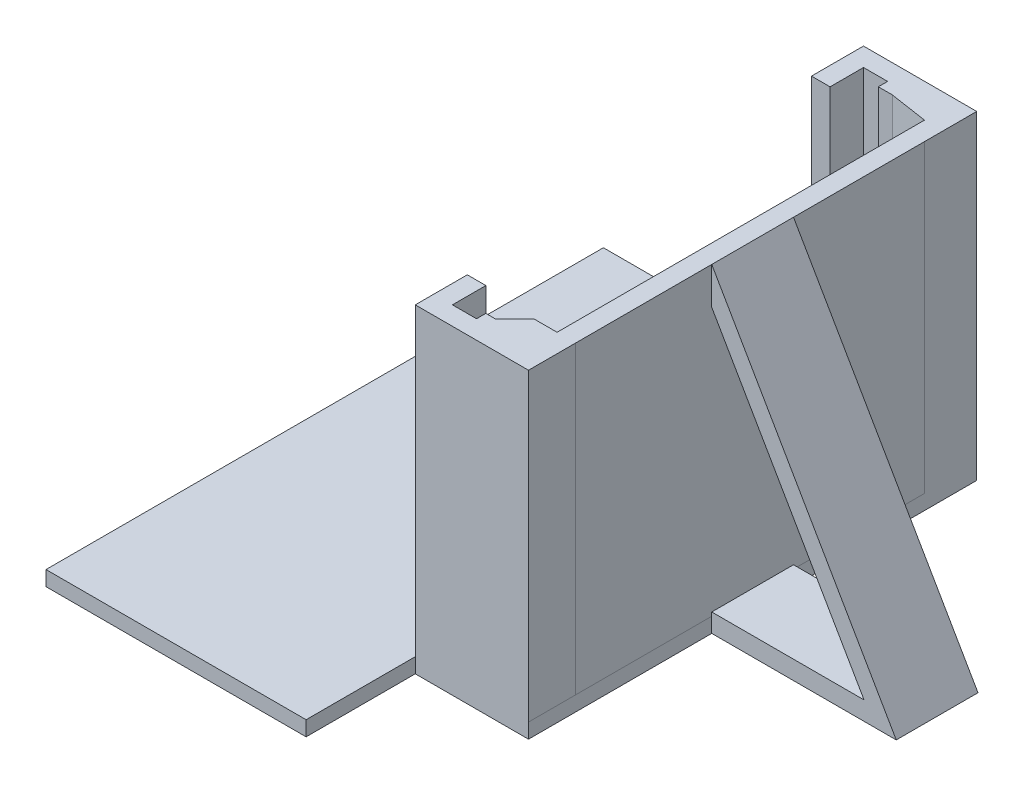
SolidWorks part; units mm, degrees
ref_plane "Front Plane" through (0, 0, 0) normal (0, 0, 1) x (1, 0, 0)
ref_plane "Top Plane" through (0, 0, 0) normal (0, 1, 0) x (1, 0, 0)
ref_plane "Right Plane" through (0, 0, 0) normal (1, 0, 0) x (0, 0, -1)
sketch "Sketch1" plane through (0, 0, 0) normal (0, 1, 0) x (1, 0, 0)
  line L1 (0, 0) -> (38.6999, 0)
  line L2 (0, 0) -> (0, 153.1937)
  line L3 (0, 153.1937) -> (38.6999, 153.1937)
  line L4 (38.6999, 0) -> (38.6999, 153.1937)
  line L5 (0, 153.1937) -> (-88.9, 153.1937)
  line L6 (0, 153.1937) -> (0, -37.3062)
  line L7 (0, -37.3062) -> (-88.9, -37.3063)
  line L8 (-88.9, 153.1937) -> (-88.9, -37.3063)
  dimension "D1" = 38.6999
  dimension "D2" = 153.1937
  dimension "D3" = 88.9
  dimension "D4" = 190.5
extrude "Boss-Extrude1" add sketch "Sketch1" along normal blind 5.08 contours L1 L4 L3 L2 | L5 L8 L7 L6 L2 region at (19.35, 0, -76.5969) region at (-44.45, 0, -57.9437)
sketch "Sketch3" plane through (0, 5.08, 0) normal (0, 1, 0) x (1, 0, 0)
  line L0 (6.65, 146.8438) -> (6.35, 146.8438)
  line L1 (6.65, 146.8438) -> (14.5875, 146.8438)
  line L2 (14.5875, 146.8438) -> (14.5875, 143.6687)
  line L3 (14.5875, 143.6687) -> (32.05, 143.6687)
  line L4 (6.35, 146.8438) -> (6.35, 135.4137)
  line L7 (32.05, 143.6687) -> (32.35, 143.6687)
  line L8 (32.35, 143.6687) -> (32.35, 135.4137)
  line L9 (32.35, 135.4137) -> (38.7, 135.4137)
  line L10 (38.7, 135.4137) -> (38.7, 153.1937)
  line L11 (38.7, 153.1937) -> (0, 153.1937)
  line L12 (6.35, 135.4137) -> (0, 135.4137)
  line L13 (0, 153.1937) -> (0, 135.4137)
  line L14 (-88.9, 153.1937) -> (38.6999, 153.1937) construction
  line L16 (14.5875, 9.525) -> (17.7625, 9.525)
  line L17 (10.6187, 146.8438) -> (10.6187, 76.5969) construction
  line L18 (10.6187, 76.5969) -> (61.4187, 76.5969) construction
  line L19 (38.6999, 0) -> (0, 0)
  line L20 (38.6999, 16.1157) -> (38.6999, 0)
  line L25 (14.5875, 6.35) -> (14.5875, 9.525)
  line L26 (6.65, 6.35) -> (14.5875, 6.35)
  line L27 (6.65, 6.35) -> (6.35, 6.35)
  line L28 (6.35, 6.35) -> (6.35, 17.78)
  line L29 (6.35, 17.78) -> (0, 17.78)
  line L30 (0, 0) -> (0, 17.78)
  line L31 (17.7625, 9.525) -> (24.3532, 16.1157)
  line L32 (24.3532, 16.1157) -> (38.6999, 16.1157)
  line L33 (19.35, 143.6687) -> (32.35, 141.6844)
  line L34 (38.6999, 0) -> (38.6999, 153.1937) construction
  point P19 (10.6187, 146.8438)
  dimension "D1" = 17.4625
  dimension "D2" = 7.9375
  dimension "D3" = 3.175
  dimension "D4" = 11.43
  dimension "D5" = 0.3
  dimension "D6" = 0.3
  dimension "D7" = 0
  dimension "D8" = 38.6999
  dimension "D9" = 6.35
  dimension "D10" = 6.35
  dimension "D11" = 6.35
  dimension "D12" = 6.35
  dimension "D13" = 70.2469
  dimension "D14" = 50.8
  dimension "D15" = 3.175
  dimension "D16" = 135
  dimension "D17" = 14.3467
  dimension "D18" = 90
  dimension "D19" = 18.08
  dimension "D20" = 90
  dimension "D21" = 4.7625
  dimension "D22" = 1.9844
extrude "Boss-Extrude2" add sketch "Sketch3" along normal blind 104.14 contours L13 L12 L4 L0 L1 L2 L3 L7 L8 L9 L10 | L30 L19 L20 L25 L26 L27 L28 L29 | L3 L33 L8 L7 region at (19.8693, 5.08, -146.5333) region at (28.0167, 5.08, -143.0073) region at (20.5173, 5.08, -7.298)
sketch "Sketch6" plane through (0, 0, -135.4137) normal (0, 0, 1) x (1, 0, 0)
  line L1 (32.35, 109.22) -> (38.7, 109.22)
  line L2 (32.35, 109.22) -> (32.35, 5.08)
  line L3 (32.35, 5.08) -> (38.7, 5.08)
  line L4 (38.7, 109.22) -> (38.7, 5.08)
  dimension "D1" = 104.14
  dimension "D2" = 6.35
extrude "Boss-Extrude3" add sketch "Sketch6" along normal up to surface (119.298 mm away) up to face at (31.5266, 57.15, -16.1157)
sketch "Sketch11" plane through (0, 0, -153.1937) normal (0, 0, -1) x (-1, 0, 0)
  line L0 (-38.6999, 109.22) -> (-101.7581, 0)
  line L1 (-38.6999, 109.22) -> (-38.6999, 0) construction
  line L4 (-38.6999, 96.52) -> (-94.4258, 0)
  line L5 (-94.4258, 0) -> (-101.7581, 0)
  line L6 (-38.6999, 96.52) -> (-38.6999, 109.22)
  line L8 (-38.6999, 109.22) -> (0, 109.22) construction
  line L9 (88.9, 0) -> (-38.6999, 0) construction
  dimension "D1" = 0
  dimension "D2" = 30
  dimension "D3" = 0
  dimension "D4" = 30
  dimension "D6" = 12.7
extrude "Boss-Extrude5" add sketch "Sketch11" along direction (0, 0, -1) on the side against the normal blind 27.94 from offset 62.6269 contours L6 L0 L5 L4 offset against normal yes
sketch "Sketch13" plane through (38.6999, 0, 0) normal (1, 0, 0) x (0, 0, -1)
  line L0 (0, 0) -> (153.1937, 0) construction
  line L1 (90.5669, 0) -> (62.6269, 0)
  line L2 (90.5669, 0) -> (90.5669, 6.35)
  line L3 (90.5669, 6.35) -> (62.6269, 6.35)
  line L4 (62.6269, 0) -> (62.6269, 6.35)
  line L5 (90.5669, 96.5199) -> (90.5669, 0) construction
  line L6 (62.6269, 109.2199) -> (62.6269, 0) construction
  dimension "D1" = 0
  dimension "D2" = 0
  dimension "D3" = 6.35
  dimension "D4" = 6.35
extrude "Boss-Extrude6" add sketch "Sketch13" along normal up to surface (63.0582 mm away) up to face at (70.2291, 54.61, -76.5969)
sketch "Sketch14" plane through (0, 0, -153.1937) normal (0, 0, -1) x (-1, 0, 0)
  line L0 (-14.5875, 5.08) -> (-6.35, 5.08) construction
  line L1 (-26, 36.83) -> (-14.5875, 36.83)
  line L2 (-26, 36.83) -> (-26, 55.88)
  line L3 (-26, 55.88) -> (-14.5875, 55.88)
  line L4 (-14.5875, 36.83) -> (-14.5875, 55.88)
  line L5 (88.9, 5.08) -> (0, 5.08) construction
  line L6 (-14.5875, 109.22) -> (-14.5875, 5.08) construction
  line L7 (-32.35, 109.22) -> (-32.35, 5.08) construction
  dimension "D1" = 31.75
  dimension "D2" = 50.8
  dimension "D3" = 0
  dimension "D4" = 6.35
extrude "Cut-Extrude1" cut sketch "Sketch14" against normal up to next
